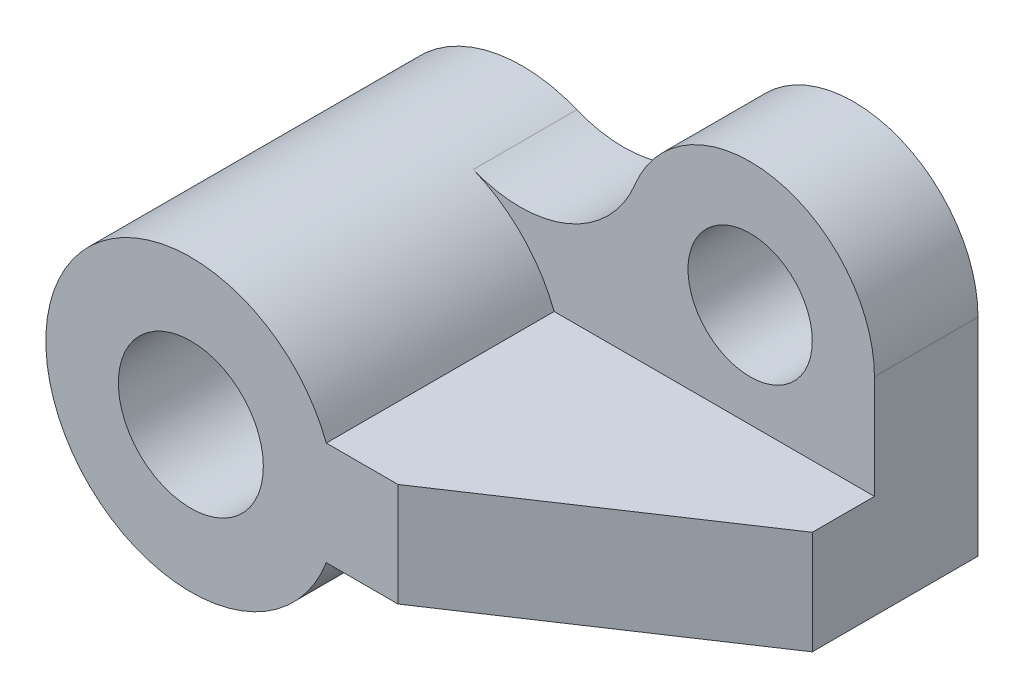
SolidWorks part; units mm, degrees
ref_plane "Front Plane" through (0, 0, 0) normal (0, 0, 1) x (1, 0, 0)
ref_plane "Top Plane" through (0, 0, 0) normal (0, 1, 0) x (1, 0, 0)
ref_plane "Right Plane" through (0, 0, 0) normal (1, 0, 0) x (0, 0, -1)
sketch "Sketch1" plane through (0, 0, 0) normal (0, 0, 1) x (1, 0, 0)
  line L0 (13.0767, -5) -> (44, -5)
  line L2 (44, -5) -> (44, 5)
  line L3 (13.0767, 5) -> (44, 5)
  line L4 (-6.9552, -0.7904) -> (44, 5) construction
  line L5 (44, -5) -> (-6.9552, 0.7904) construction
  line L7 (44, 5) -> (20, 5)
  line L8 (44, 5) -> (44, 15)
  circle A0 centre (0, 0) radius 7
  arc A1 (13.0767, 5) -> (13.0767, -5) centre (0, 0) ccw
  arc A2 (44, 15) -> (20.8935, 19.5438) centre (32, 15) ccw
  circle A3 centre (32, 15) radius 6
  arc A4 (5.27, 12.9703) -> (20.8935, 19.5438) centre (9.7871, 24.0876) ccw
  dimension "D1" = 14
  dimension "D2" = 28
  dimension "D7" = 12
  dimension "D8" = 12
  dimension "D3" = 44
  dimension "D4" = 10
  dimension "D5" = 20
extrude "Boss-Extrude1" add sketch "Sketch1" along normal blind 32 contours L3 A1 L0 L2 A0 region at (11.4293, 0, 0)
extrude "Boss-Extrude2" add sketch "Sketch1<3>" along normal blind 10 contours A4 A1 L3 L8 A2 A3 region at (14.6136, 12.6162, 0)
sketch "Sketch1<3>" plane through (0, 0, 0) normal (0, 0, 1) x (1, 0, 0) same geometry as "Sketch1"
chamfer "Chamfer1" distance 16 distance2 24 1 edges at (44, 0, 32) first distance on face at (44, 5, 14)
